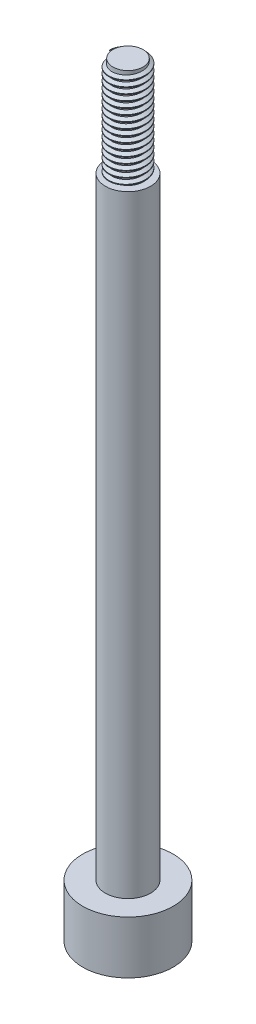
SolidWorks part; units mm, degrees
ref_plane "Plan de face" through (0, 0, 0) normal (0, 0, 1) x (1, 0, 0)
ref_plane "Plan de dessus" through (0, 0, 0) normal (0, 1, 0) x (1, 0, 0)
ref_plane "Plan de droite" through (0, 0, 0) normal (1, 0, 0) x (0, 0, -1)
sketch "Esquisse1" plane through (0, 0, 0) normal (0, 0, 1) x (1, 0, 0)
  line L0 (0, 0) -> (3, 0)
  line L1 (0, 0) -> (3, 0) construction
  line L2 (0, 0) -> (0, 50.7) construction
  line L3 (0, 50.7) -> (3, 50.7) construction
  line L4 (3, 0) -> (3, 50.7) construction
  line L5 (3, 0) -> (3, 3.5)
  line L6 (3, 3.5) -> (1.5, 3.5)
  line L9 (0, 50.7) -> (0, 0)
  line L10 (1.5, 3.5) -> (1.5, 44.1)
  line L11 (1.5, 44.1) -> (1, 44.1)
  line L12 (1, 44.1) -> (1, 50.7)
  line L13 (0, 50.7) -> (1, 50.7)
  dimension "D1" = 3
  dimension "D2" = 50.7
  dimension "D3" = 3.5
  dimension "D4" = 1.5
  dimension "D5" = 6.6
  dimension "D6" = 1
revolve "Révolution1" add sketch "Esquisse1" angle 360 about L9
thread "Filetage1" pitch 0.4 method extrude profile "Profil de filetage2" start angle 0, offset 0, length 6.6, pitch 0.4, diameter 2
ref_plane "Plan2" through (-1, 50.7, 0) normal (0, 0, 1) x (-1, 0, 0)
sketch "Profil de filetage2" plane through (-1, 50.7, 0) normal (0, 0, 1) x (-1, 0, 0)
  line L0 (0, 0) -> (0, 0.4) construction
  line L1 (0, 0) -> (0.2165, 0.125)
  line L2 (0.2165, 0.125) -> (0.2165, 0.175)
  line L3 (0.2165, 0.175) -> (0, 0.3)
  line L4 (0.2165, 0.15) -> (0, 0.15) construction
  line L11 (0, 0) -> (0, 0.3)
  point P2 (0, 0)
  dimension "Pitch" = 0.4
  dimension "Profile_Angle" = 60
  dimension "Profile_Land" = 0.05
  dimension "Profile_Height" = 0.2165
sketch "Esquisse9" plane through (0, 0, 0) normal (0, -1, 0) x (1, 0, 0)
  line L0 (0, 0) -> (0, 2.5619) construction
  line L1 (1.299, 0.75) -> (0, 1.5)
  line L2 (0, 1.5) -> (-1.299, 0.75)
  line L3 (-1.299, 0.75) -> (-1.299, -0.75)
  line L4 (-1.299, -0.75) -> (0, -1.5)
  line L5 (0, -1.5) -> (1.299, -0.75)
  line L6 (1.299, -0.75) -> (1.299, 0.75)
  circle A0 centre (0, 0) radius 1.5 construction
  dimension "D1" = 3
extrude "Enlèv. mat.-Extru.1" cut sketch "Esquisse9" against normal blind 2.6
